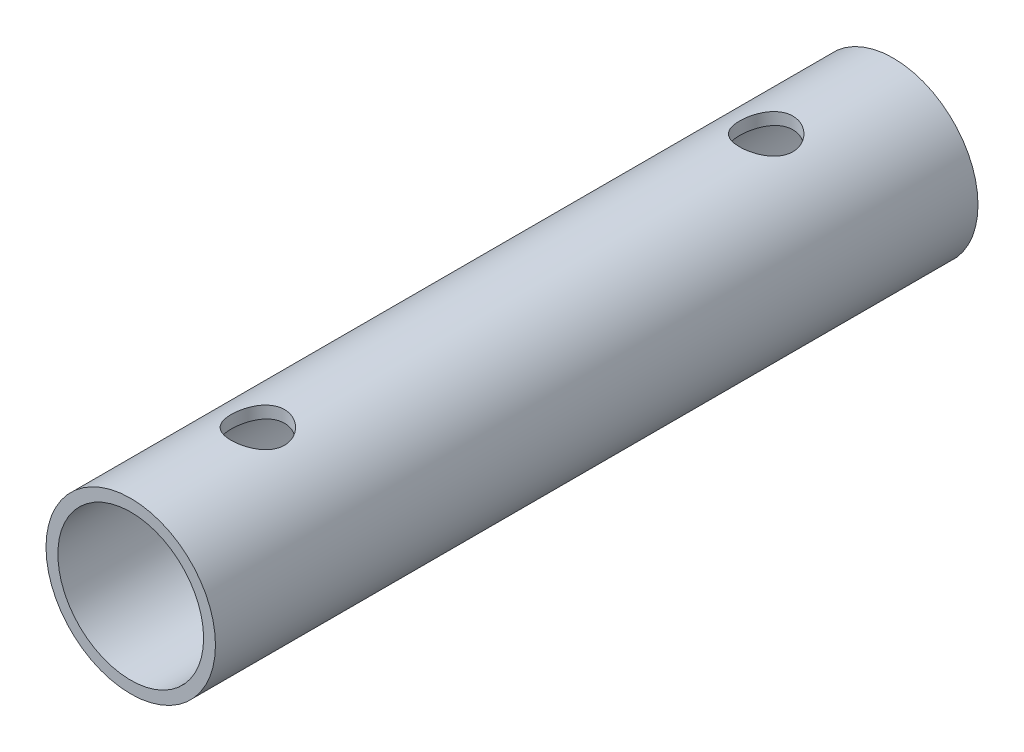
SolidWorks part; units mm, degrees
ref_plane "Front" through (0, 0, 0) normal (0, 0, 1) x (1, 0, 0)
ref_plane "Top" through (0, 0, 0) normal (0, 1, 0) x (1, 0, 0)
ref_plane "Right" through (0, 0, 0) normal (1, 0, 0) x (0, 0, -1)
sketch "Sketch1" plane through (0, 0, 0) normal (0, 0, 1) x (1, 0, 0)
  circle A0 centre (0, 0) radius 6.35
  circle A1 centre (0, 0) radius 5.461
extrude "Extrude1" add sketch "Sketch1" along normal blind 57.15
sketch "Sketch2" plane through (0, 0, 0) normal (0, 1, 0) x (1, 0, 0)
  line L0 (0, 0) -> (0, -9.525)
  line L2 (-6.35, -57.15) -> (6.35, -57.15) construction
  line L3 (0, -57.15) -> (0, -47.625)
  circle A0 centre (0, -9.525) radius 2
  circle A1 centre (0, -47.625) radius 2
extrude "Cut-Extrude1" cut sketch "Sketch2" against normal blind 38.1 and the other way blind 38.1
